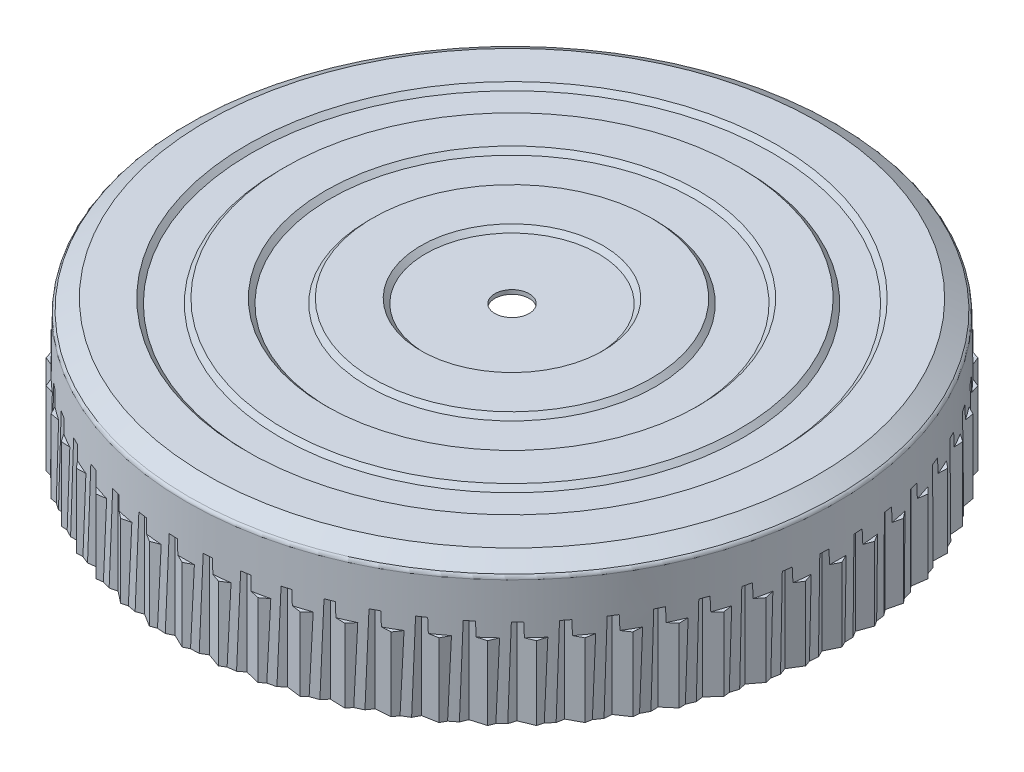
SolidWorks part; units mm, degrees
material "Steel ASTM A36"
ref_plane "Front Plane" through (0, 0, 0) normal (0, 0, 1) x (1, 0, 0)
ref_plane "Top Plane" through (0, 0, 0) normal (0, 1, 0) x (1, 0, 0)
ref_plane "Right Plane" through (0, 0, 0) normal (1, 0, 0) x (0, 0, -1)
sketch "Sketch1" plane through (0, 0, 0) normal (0, 0, 1) x (1, 0, 0)
  line L0 (0, 0) -> (0, 71.6894) construction
  line L1 (0, 0.762) -> (16.002, 0.762)
  line L2 (60.198, -0.5334) -> (60.579, -23.7619)
  line L3 (21.3106, 1.6256) -> (21.3106, 0.8636) construction
  line L4 (16.002, 0.762) -> (16.8656, 1.6256)
  line L5 (0, 0.762) -> (0, 0)
  line L6 (60.579, -23.7619) -> (59.8171, -23.7744)
  line L7 (16.8656, 1.6256) -> (25.7556, 1.6256)
  line L8 (25.7556, 1.6256) -> (26.6192, 0.762)
  line L9 (26.6192, 0.762) -> (33.655, 0.762)
  line L10 (33.655, 0.762) -> (34.5186, 1.6256)
  line L11 (34.5186, 1.6256) -> (42.037, 1.6256)
  line L12 (42.037, 1.6256) -> (42.9006, 0.762)
  line L13 (42.9006, 0.762) -> (48.26, 0.762)
  line L14 (48.26, 0.762) -> (49.1236, 1.6256)
  line L15 (49.1236, 1.6256) -> (56.642, 1.6256)
  line L16 (56.642, 1.6256) -> (60.198, -0.5334)
  line L17 (0, 0) -> (16.3176, 0)
  line L18 (16.3176, 0) -> (17.1812, 0.8636)
  line L19 (17.1812, 0.8636) -> (25.44, 0.8636)
  line L20 (25.44, 0.8636) -> (26.3036, 0)
  line L21 (26.3036, 0) -> (33.9706, 0)
  line L22 (33.9706, 0) -> (34.8342, 0.8636)
  line L23 (34.8342, 0.8636) -> (41.7214, 0.8636)
  line L24 (41.7214, 0.8636) -> (42.585, 0)
  line L25 (42.585, 0) -> (48.4732, 0)
  line L26 (48.4732, 0) -> (49.3368, 0.8636)
  line L27 (49.3368, 0.8636) -> (56.4288, 0.8636)
  line L28 (56.4288, 0.8636) -> (59.443, -0.9665)
  line L29 (59.443, -0.9665) -> (59.8171, -23.7744)
  line L30 (38.2778, 1.6256) -> (38.2778, 0.8636) construction
  line L31 (52.8828, 1.6256) -> (52.8828, 0.8636) construction
  dimension "D5" = 0.8636
  dimension "D1" = 121.158
  dimension "D2" = 120.396
  dimension "D3" = 0.762
  dimension "D4" = 32.004
  dimension "D6" = 10.6172
  dimension "D7" = 67.31
  dimension "D8" = 96.52
  dimension "D9" = 9.2456
  dimension "D10" = 25.4
  dimension "D11" = 0.762
  dimension "D12" = 2.159
  dimension "D13" = 0.762
  dimension "D14" = 0.762
  dimension "D15" = 0.762
revolve "Revolve1" add sketch "Sketch1" angle 360 about L0
sketch "Sketch2" plane through (0, 0, 0) normal (0, 1, 0) x (1, 0, 0)
  circle A0 centre (0, 0) radius 3.175
  dimension "D1" = 6.35
extrude "Cut-Extrude1" cut sketch "Sketch2" along normal through all
fillet "Fillet1" radius 0.7937 2 edges at (0, -0.9665, -59.443) (0, -0.5334, -60.198)
ref_plane "Plane1" through (0, -25.4, 0) normal (0, 1, 0) x (1, 0, 0)
sketch "Sketch3" plane through (0, -25.4, 0) normal (0, 1, 0) x (1, 0, 0)
  line L0 (59.8107, -0.8749) -> (60.2387, 0)
  line L1 (60.5698, -1.0572) -> (61.087, 0)
  line L2 (61.087, 0) -> (60.5698, 1.0572) construction
  line L3 (60.5698, -1.0572) -> (0, 0) construction
  line L4 (0, 0) -> (60.5698, 1.0572) construction
  line L5 (60.5698, -1.0572) -> (59.8638, -2.5002)
  line L6 (60.2387, 0) -> (59.8107, 0.8749)
  line L7 (59.8638, -2.5002) -> (60.5698, -3.9432)
  line L8 (59.8107, -0.8749) -> (59.0155, -2.5002) construction
  line L9 (59.0155, -2.5002) -> (59.6911, -3.881) construction
  line L10 (59.6911, -3.881) -> (59.8107, -0.8749) construction
  line L11 (60.2387, 0) -> (61.087, 0) construction
  line L12 (60.5698, 1.0572) -> (60.5698, -1.0572) construction
  line L13 (59.8107, 0.8749) -> (59.0155, 2.5002)
  line L14 (59.0155, 2.5002) -> (59.0155, -2.5002)
  line L15 (59.0155, -2.5002) -> (59.8107, -0.8749)
  line L16 (61.087, 0) -> (61.087, -5.0004)
  line L17 (61.087, -5.0004) -> (60.5698, -3.9432)
  circle A0 centre (0, 0) radius 60.579 construction
  circle A1 centre (0, 0) radius 59.8171 construction
  circle A3 centre (0, 0) radius 59.0685 construction
  dimension "D1" = 2
  dimension "D2" = 0.762
  dimension "D3" = 61.087
  dimension "D4" = 0.762
extrude "Cut-Extrude2" cut sketch "Sketch3" along normal blind 17.78
sketch "Sketch4" plane through (0, -25.4, 0) normal (0, 1, 0) x (1, 0, 0)
  line L0 (59.8107, -0.8749) -> (59.0155, -2.5002)
  line L1 (59.0155, -2.5002) -> (59.6911, -3.881)
  line L2 (60.5698, -1.0572) -> (61.087, 0)
  line L3 (61.087, 0) -> (60.5698, 1.0572)
  line L4 (60.5698, 1.0572) -> (60.2387, 1.734)
  line L5 (60.2387, 1.734) -> (60.2387, 0)
  line L6 (60.5698, -1.0572) -> (59.8638, -2.5002)
  line L7 (59.8638, -2.5002) -> (59.8638, -4.2342)
  line L8 (59.8638, -4.2342) -> (59.6911, -3.881)
  line L9 (59.8107, -0.8749) -> (60.2387, 0)
extrude "Boss-Extrude1" add sketch "Sketch4" along normal blind 15.24
pattern_circular "CirPattern1" count 60 over 360 about axis through (0, 0, 0) along (0, 1, 0) of "Cut-Extrude2", "Boss-Extrude1"
sketch "Sketch5" plane through (0, 0, 0) normal (0, 0, 1) x (1, 0, 0)
  line L0 (63.5, -23.714) -> (0, -24.7555)
  line L1 (0, -23.7744) -> (0, -10.16) construction
  line L2 (0, -24.7555) -> (0, -30.064)
  line L3 (0, -30.064) -> (63.5, -30.064)
  line L4 (63.5, -30.064) -> (63.5, -23.714)
  line L5 (60.579, -23.7619) -> (59.8171, -23.7744) construction
  dimension "D1" = 63.5
  dimension "D2" = 6.35
revolve "Cut-Revolve1" cut sketch "Sketch5" angle 360 about axis through (0, -0.9665, 0) along (0, -1, 0)
